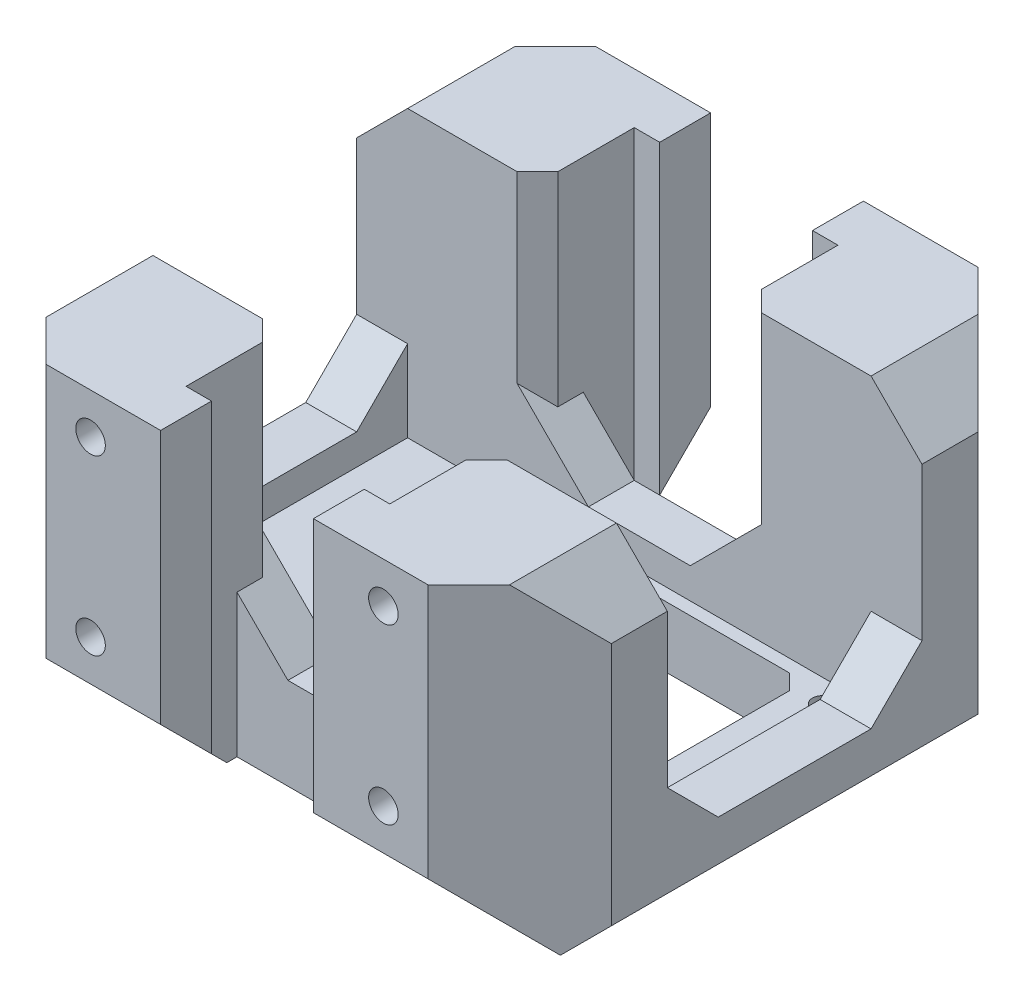
SolidWorks part; units mm, degrees
ref_plane "Front Plane" through (0, 0, 0) normal (0, 0, 1) x (1, 0, 0)
ref_plane "Top Plane" through (0, 0, 0) normal (0, 1, 0) x (1, 0, 0)
ref_plane "Right Plane" through (0, 0, 0) normal (1, 0, 0) x (0, 0, -1)
sketch "Sketch1" plane through (0, 0, 0) normal (0, 1, 0) x (1, 0, 0)
  line L0 (-27.75, -17.5) -> (-27.75, 17.5)
  line L1 (-22.75, -12.5) -> (22.75, -12.5)
  line L2 (-22.75, -12.5) -> (-22.75, 12.5)
  line L3 (-22.75, 12.5) -> (22.75, 12.5)
  line L4 (22.75, -12.5) -> (22.75, 12.5)
  line L5 (-22.75, -12.5) -> (22.75, 12.5) construction
  line L6 (-22.75, 12.5) -> (22.75, -12.5) construction
  line L7 (-27.75, 17.5) -> (27.75, 17.5)
  line L8 (27.75, -17.5) -> (27.75, 17.5)
  line L9 (-27.75, -17.5) -> (27.75, -17.5)
  point P0 (0, 0)
  dimension "D1" = 45.5
  dimension "D2" = 25
  dimension "D3" = 5
extrude "Boss-Extrude1" add sketch "Sketch1" along normal blind 28
sketch "Sketch2" plane through (0, 0, 0) normal (0, -1, 0) x (1, 0, 0)
  line L0 (-27.75, 17.5) -> (27.75, 17.5) construction
  line L1 (-27.75, 17.5) -> (27.75, 17.5)
  line L2 (-27.75, -17.5) -> (-27.75, 17.5) construction
  line L3 (27.75, -17.5) -> (-27.75, -17.5) construction
  line L4 (27.75, 17.5) -> (27.75, -17.5) construction
  line L5 (-27.75, -17.5) -> (-27.75, 17.5)
  line L6 (27.75, -17.5) -> (-27.75, -17.5)
  line L7 (27.75, 17.5) -> (27.75, -17.5)
extrude "Boss-Extrude2" add sketch "Sketch2" along normal blind 6
sketch "Sketch4" plane through (0, 0, 0) normal (0, 1, 0) x (1, 0, 0)
  line L0 (22.75, -12.5) -> (22.75, 12.5) construction
  line L1 (-4.2, -10.25) -> (20.25, -10.25) construction
  line L2 (-4.2, -10.25) -> (-4.2, 10.25) construction
  line L3 (-4.2, 10.25) -> (20.25, 10.25) construction
  line L4 (20.25, -10.25) -> (20.25, 10.25) construction
  line L5 (-4.2, -10.25) -> (20.25, 10.25) construction
  line L6 (-4.2, 10.25) -> (20.25, -10.25) construction
  circle A0 centre (-4.2, 10.25) radius 1
  circle A1 centre (20.25, 10.25) radius 1
  circle A2 centre (20.25, -10.25) radius 1
  circle A3 centre (-4.2, -10.25) radius 1
  point P0 (8.025, 0)
  dimension "D1" = 2
  dimension "D2" = 20.5
  dimension "D3" = 24.45
  dimension "D4" = 2.5
extrude "Cut-Extrude1" cut sketch "Sketch4" against normal blind 3.5
sketch "Sketch5" plane through (0, -3.5, 0) normal (0, 1, 0) x (1, 0, 0)
  circle A0 centre (-4.2, 10.25) radius 2
  circle A1 centre (20.25, 10.25) radius 2
  circle A2 centre (20.25, -10.25) radius 2
  circle A3 centre (-4.2, -10.25) radius 2
  dimension "D1" = 4
extrude "Cut-Extrude2" cut sketch "Sketch5" against normal up to next
sketch "Sketch6" plane through (0, 0, 0) normal (0, 1, 0) x (1, 0, 0)
  line L1 (-1.75, -11.25) -> (17.5, -11.25)
  line L2 (-1.75, -11.25) -> (-1.75, 11.25)
  line L3 (-1.75, 11.25) -> (17.5, 11.25)
  line L4 (17.5, -11.25) -> (17.5, 11.25)
  line L5 (-1.75, -11.25) -> (17.5, 11.25) construction
  line L6 (-1.75, 11.25) -> (17.5, -11.25) construction
  circle A0 centre (20.25, 10.25) radius 1 construction
  point P0 (7.875, 0)
  dimension "D1" = 22.5
  dimension "D2" = 19.25
  dimension "D3" = 2.75
extrude "Cut-Extrude3" cut sketch "Sketch6" against normal up to next
chamfer "Chamfer1" distance 1.5 angle 45 4 edges at (-1.75, -3, 11.25) (17.5, -3, 11.25) (-1.75, -3, -11.25) (17.5, -3, -11.25)
sketch "Sketch7" plane through (0, 0, 0) normal (0, 1, 0) x (1, 0, 0)
  line L0 (-1.75, 9.75) -> (-1.75, -9.75) construction
  circle A0 centre (-12.5, 0) radius 3
  dimension "D1" = 6
  dimension "D2" = 10.75
extrude "Cut-Extrude4" cut sketch "Sketch7" against normal up to next
chamfer "Chamfer2" distance 1 angle 45 2 edges at (-12.5, -6, 3) (-12.5, 0, 3)
sketch "Sketch8" plane through (0, 28, 0) normal (0, 1, 0) x (1, 0, 0)
  line L6 (27.75, -17.5) -> (27.75, 17.5) construction
  line L7 (-27.75, -17.5) -> (27.75, -17.5)
  line L8 (-27.75, -17.5) -> (-27.75, -27)
  line L9 (-27.75, -27) -> (27.75, -27)
  line L10 (27.75, -17.5) -> (27.75, -27)
  dimension "D1" = 9.5
extrude "Boss-Extrude3" add sketch "Sketch8" against normal up to surface (34 mm away) up to face at (-12.5, -6, 4)
sketch "Sketch10" plane through (0, 28, 0) normal (0, 1, 0) x (1, 0, 0)
  line L0 (-27.75, -27) -> (27.75, -27) construction
  line L1 (-10, -17) -> (10, -17)
  line L2 (-10, -17) -> (-10, -22)
  line L3 (-10, -22) -> (10, -22)
  line L4 (10, -17) -> (10, -22)
  line L5 (-10, -17) -> (10, -22) construction
  line L6 (-10, -22) -> (10, -17) construction
  line L7 (-7.5, -27) -> (7.5, -27)
  line L8 (-7.5, -27) -> (-7.5, -22)
  line L9 (-7.5, -22) -> (7.5, -22)
  line L10 (7.5, -27) -> (7.5, -22)
  line L11 (-7.5, -27) -> (7.5, -22) construction
  line L12 (-7.5, -22) -> (7.5, -27) construction
  point P0 (0, -19.5)
  point P5 (0, -24.5)
  point P15 (-7.5, -24.5)
  line M10 (-27.75, -27) -> (27.75, -27)
  dimension "D1" = 5
  dimension "D2" = 20
  dimension "D3" = 15
extrude "Cut-Extrude5" cut sketch "Sketch10" against normal up to next contours L4 L1 L2 L3 | L10 L3 L8 M10 region at (0, 28, 19.5) region at (0, 28, 24.5)
mirror "Mirror3" about plane through (0, 0, 0) normal (0, 0, 1) of "Cut-Extrude5", "Boss-Extrude3"
chamfer "Chamfer7" distance 9 angle 45 8 edges at (17.625, -6, -27) (27.75, 11, -27) (-17.625, -6, -27) (-27.75, 11, -27) (17.625, -6, 27) (27.75, 11, 27) (-17.625, -6, 27) (-27.75, 11, 27)
chamfer "Chamfer8" distance 5 angle 45 2 edges at (27.75, 28, 0) (-27.75, 28, 0)
chamfer "Chamfer9" distance 5 angle 45 2 edges at (27.75, -6, 0) (-27.75, -6, 0)
sketch "Sketch12" plane through (0, 0, -27) normal (0, 0, -1) x (-1, 0, 0)
  line L0 (18.75, 28) -> (7.5, 28) construction
  line L1 (-14.375, 7) -> (14.375, 7) construction
  line L2 (-14.375, 7) -> (-14.375, 24) construction
  line L3 (-14.375, 24) -> (14.375, 24) construction
  line L4 (14.375, 7) -> (14.375, 24) construction
  line L5 (-14.375, 7) -> (14.375, 24) construction
  line L6 (-14.375, 24) -> (14.375, 7) construction
  line L7 (7.5, 3) -> (18.75, 3) construction
  circle A0 centre (-14.375, 24) radius 1.45
  circle A1 centre (14.375, 24) radius 1.45
  circle A2 centre (14.375, 7) radius 1.45
  circle A3 centre (-14.375, 7) radius 1.45
  point P0 (0, 15.5)
  dimension "D1" = 2.9
  dimension "D3" = 4
  dimension "D4" = 4
  dimension "D2" = 28.75
extrude "Cut-Extrude7" cut sketch "Sketch12" against normal blind 8
mirror "Mirror4" about plane through (0, 0, 0) normal (0, 0, 1) of "Cut-Extrude7"
sketch "Sketch13" plane through (0, 0, -12.5) normal (0, 0, 1) x (1, 0, 0)
  line L0 (10, -6) -> (10, 28) construction
  line L1 (-10, 28) -> (10, 28)
  line L2 (-10, 28) -> (-10, 3)
  line L3 (-10, 3) -> (10, 3)
  line L4 (10, 28) -> (10, 3)
  line L6 (18.75, 3) -> (7.5, 3) construction
extrude "Cut-Extrude8" cut sketch "Sketch13" against normal up to next
sketch "Sketch14" plane through (22.75, 0, 0) normal (-1, 0, 0) x (0, 0, 1)
  line L0 (12.5, 28) -> (12.5, 0) construction
  line L1 (-12.5, 28) -> (12.5, 28)
  line L2 (-12.5, 28) -> (-12.5, 3)
  line L3 (-12.5, 3) -> (12.5, 3)
  line L4 (12.5, 28) -> (12.5, 3)
  line L5 (-17, 3) -> (-12.5, 3) construction
extrude "Cut-Extrude9" cut sketch "Sketch14" against normal up to next
mirror "Mirror5" about plane through (0, 0, 0) normal (1, 0, 0) of "Cut-Extrude9"
mirror "Mirror6" about plane through (0, 0, 0) normal (0, 0, 1) of "Cut-Extrude8"
chamfer "Chamfer10" distance 5 angle 45 8 edges at (-25.25, 3, 12.5) (-25.25, 3, -12.5) (-10, 3, 14.75) (10, 3, 14.75) (25.25, 3, 12.5) (25.25, 3, -12.5) (-10, 3, -14.75) (10, 3, -14.75)
chamfer "Chamfer11" distance 2 angle 45 4 edges at (10, 18, -12.5) (-10, 18, 12.5) (-10, 18, -12.5) (10, 18, 12.5)
